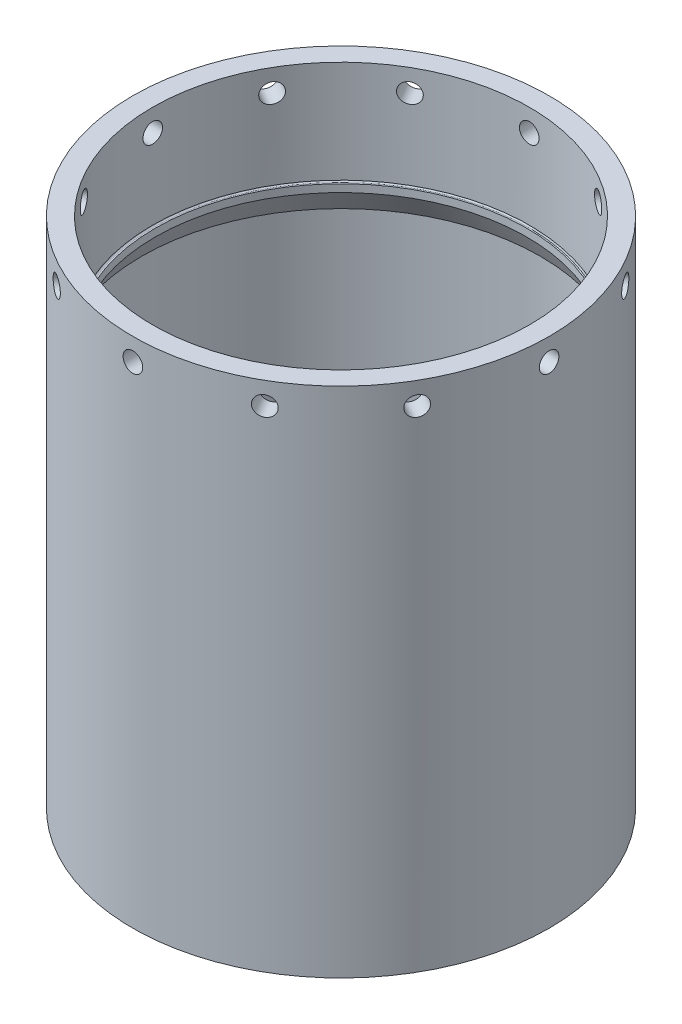
SolidWorks part; units mm, degrees
material "AISI 304"
ref_plane "Front Plane" through (0, 0, 0) normal (0, 0, 1) x (1, 0, 0)
ref_plane "Top Plane" through (0, 0, 0) normal (0, 1, 0) x (1, 0, 0)
ref_plane "Right Plane" through (0, 0, 0) normal (1, 0, 0) x (0, 0, -1)
sketch "Sketch2" plane through (0, 0, 0) normal (0, 0, 1) x (1, 0, 0)
  line L4 (0, 0) -> (0, -101.6) construction
  line L6 (61.849, 0) -> (62.738, 0)
  line L7 (61.849, 0) -> (61.849, -2.54)
  line L8 (57.15, -136.1974) -> (69.342, -136.1974)
  line L9 (69.342, 34.417) -> (69.342, -136.1974)
  line L12 (62.738, 0) -> (62.738, 34.417)
  line L13 (62.738, 34.417) -> (69.342, 34.417)
  line L14 (61.849, -2.54) -> (66.3575, -10.349)
  line L15 (66.3575, -10.349) -> (66.3575, -111.949)
  line L17 (59.69, -131.798) -> (59.69, -123.4974)
  line L18 (59.69, -123.4974) -> (66.3575, -111.949)
  line L19 (59.69, -131.798) -> (57.15, -136.1974)
  dimension "D5" = 34.417
  dimension "D7" = 125.476
  dimension "D2" = 123.698
  dimension "D4" = 132.715
  dimension "D9" = 30
  dimension "D10" = 2.54
  dimension "D11" = 30
  dimension "D14" = 119.38
  dimension "D15" = 114.3
  dimension "D16" = 30
  dimension "D12" = 12.7
  dimension "D6" = 101.6
  dimension "D13" = 170.6144
  dimension "D3" = 138.684
revolve "Revolve1" add sketch "Sketch2" angle 360 about L4
fillet "Fillet1" radius 0.4064 1 edges at (-62.738, 0, 0)
ref_plane "Plane1" through (0, 0, 69.342) normal (0, 0, 1) x (1, 0, 0)
sketch "Sketch3" plane through (0, 0, 69.342) normal (0, 0, 1) x (1, 0, 0)
  line L1 (62.3316, 0) -> (-62.3316, 0) construction
  point P0 (0, 27.0256)
  dimension "D1" = 27.0256
hole_wizard "F (0.257) Injector Hole" positions "Sketch3" profile "Sketch4" hole size "F" standard "ANSI Inch" end condition up to next
sketch "Sketch4" plane through (0, 27.0256, 69.342) normal (1, 0, 0) x (0, -1, 0)
  line L0 (0, 0) -> (0, 6.604)
  line L1 (0, 6.604) -> (3.2639, 6.604)
  line L2 (3.2639, 6.604) -> (3.2639, 0)
  line L5 (3.2639, 0) -> (0, 0)
  line L11 (0, -6.35) -> (0, 107.95) construction
  dimension "Thru Hole Dia." = 6.5278
  dimension "Thru Hole Depth" = 6.604
sketch "Sketch5" plane through (0, -136.1974, 0) normal (0, -1, 0) x (1, 0, 0)
  line L0 (0, 64.516) -> (-61.3584, 19.9365) construction
  line L1 (-61.3584, 19.9365) -> (-37.9216, -52.1945) construction
  line L2 (-37.9216, -52.1945) -> (37.9216, -52.1945) construction
  line L3 (37.9216, -52.1945) -> (61.3584, 19.9365) construction
  line L4 (61.3584, 19.9365) -> (0, 64.516) construction
  circle A1 centre (0, 0) radius 64.516 construction
  point P0 (0, 64.516)
  point P8 (61.3584, 19.9365)
  point P10 (37.9216, -52.1945)
  point P12 (-37.9216, -52.1945)
  point P14 (-61.3584, 19.9365)
  dimension "D1" = 129.032
hole_wizard "1/4-20 Tapped Nozzle Hole" positions "Sketch5" profile "Sketch6" tap size "1/4-20" standard "ANSI Inch"
sketch "Sketch6" plane through (0, -136.1974, 64.516) normal (1, 0, 0) x (0, 0, -1)
  line L0 (0, 0) -> (0, 14.2338)
  line L1 (0, 14.2338) -> (2.5527, 12.7)
  line L2 (2.5527, 12.7) -> (2.5527, 6.985)
  line L3 (2.5527, 6.985) -> (3.175, 6.985)
  line L4 (3.175, 6.985) -> (3.175, 0)
  line L5 (3.175, 0) -> (0, 0)
  line L10 (0, 14.2338) -> (-2.5527, 12.7) construction
  line L11 (0, -6.35) -> (0, 107.95) construction
  dimension "Tap Drill Dia." = 5.1054
  dimension "Tap Drill Depth" = 12.7
  dimension "Thread Major Dia." = 6.35
  dimension "Thread Depth" = 6.985
  dimension "Drill Angle" = 118
pattern_circular "CirPattern1" count 12 over 360 about axis through (0, 0, 0) along (0, 1, 0) of "F (0.257) Injector Hole" reverse direction yes
equation "\"length\"= 4in"
equation "\"bearingThickness\"= 0.178in"
equation "\"chamberID\"=5.225"
equation "\"D4@Sketch2\"=\"chamberID\""
equation "\"D6@Sketch2\"=\"length\""
equation "\"D1@Sketch3\"=1.06in+0.004"
